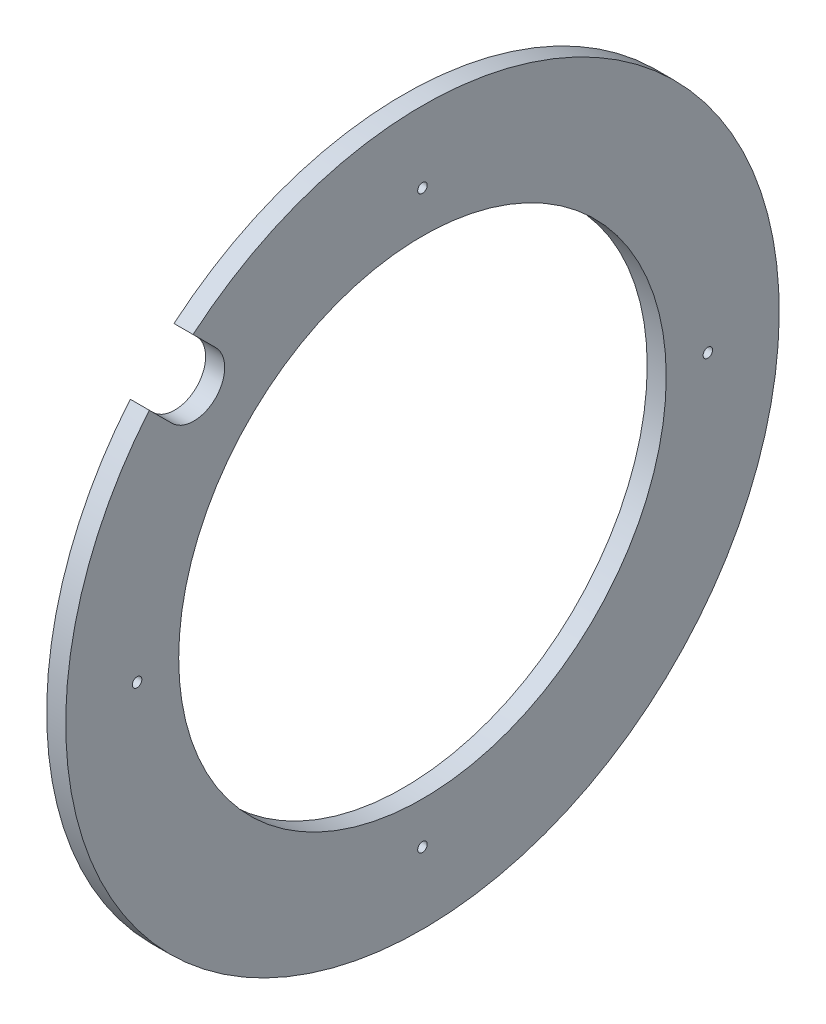
SolidWorks part; units mm, degrees
material "Teck"
ref_plane "Plan de face" through (0, 0, 0) normal (0, 0, 1) x (1, 0, 0)
ref_plane "Plan de dessus" through (0, 0, 0) normal (0, 1, 0) x (1, 0, 0)
ref_plane "Plan de droite" through (0, 0, 0) normal (1, 0, 0) x (0, 0, -1)
sketch "Esquisse1" plane through (0, 0, 0) normal (1, 0, 0) x (0, 0, -1)
  circle A0 centre (0, 0) radius 51.25
  circle A1 centre (0, 0) radius 75
  dimension "D1" = 102.5
  dimension "D2" = 150
extrude "Boss.-Extru.1" add sketch "Esquisse1" along normal blind 4
sketch "Sketch1" plane through (4, 0, 0) normal (1, 0, 0) x (0, 0, -1)
  circle A0 centre (0, 60) radius 1
  circle A1 centre (60, 0) radius 1
  circle A2 centre (0, -60) radius 1
  circle A3 centre (-60, 0) radius 1
  point P11 (0, 0)
  dimension "D2" = 2
  dimension "D3" = 60
  dimension "D1" = 4
extrude "air vents" cut sketch "Sketch1" against normal through all
sketch "Sketch2" plane through (4, 0, 0) normal (1, 0, 0) x (0, 0, -1)
  line L0 (0, 0) -> (-48.0833, 48.0833) construction
  line L1 (-43.4871, 52.6795) -> (-81.6004, 90.7927)
  line L2 (-52.6795, 43.4871) -> (-92.274, 83.0816)
  line L3 (-92.274, 83.0816) -> (-81.6004, 90.7927)
  line L4 (0, 0) -> (0, 42.3711) construction
  arc A0 (-52.6795, 43.4871) -> (-43.4871, 52.6795) centre (-48.0833, 48.0833) ccw
  dimension "D1" = 13
  dimension "D2" = 68
  dimension "D3" = 45
extrude "Cut-Extrude1" cut sketch "Sketch2" against normal blind 10
equation "\"d_i_tube\"= 150mm'Inner Rocket Body Composite Tube Diameter"
equation "\"t_tube\"= 1.182mm'Thickness of Rocket Body Composite Tube"
equation "\"l_upper_body_tube\"= 1190mm'Upper Rocket Body Composite Tube length"
equation "\"l_lower_body_tube\"= 896mm'Lower Rocket Body Composite Tube Length"
equation "\"d_a_NC\"= 154mm'Outer Diameter of Nosecone base"
equation "\"d_i_phenolic_tube\"= 152.3mm'Inner Phenolic Tube Diameter"
equation "\"t_phenolic_tube\"= 2mm'Thickness of Phenolic Body Tube"
equation "\"l_fin_cut\"= 220mm'Length of fin on Motor Retainer"
equation "\"t_SW-Panel\"= 11.482mm'Thickness of Sandwich-Panel"
equation "\"l_motor_tube\"=650mm'Length of phenolic motor tube"
equation "\"d_i_motor_tube\"=99.06mm'Inner diameter of phenolic motor tube"
equation "\"t_motor_tube\"=1.58mm'Thicknes of phenolic motor tube"
equation "\"D2@Esquisse1\"=\"d_i_tube\""
